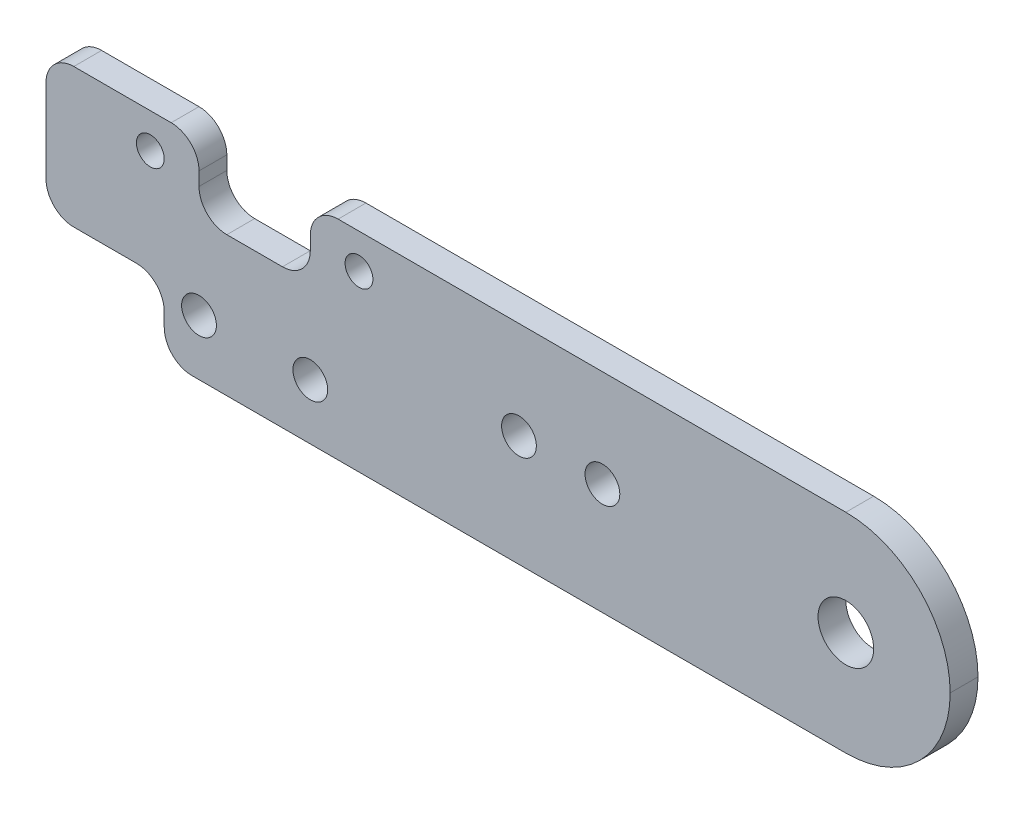
SolidWorks part; units mm, degrees
material "Thornel Mat VMA"
ref_plane "前视基准面" through (0, 0, 0) normal (0, 0, 1) x (1, 0, 0)
ref_plane "上视基准面" through (0, 0, 0) normal (0, 1, 0) x (1, 0, 0)
ref_plane "右视基准面" through (0, 0, 0) normal (1, 0, 0) x (0, 0, -1)
sketch "草图1" plane through (0, 0, 0) normal (0, 0, 1) x (1, 0, 0)
  line L1 (-32.5, -7.5) -> (32.5, -7.5)
  line L2 (-32.5, -7.5) -> (-32.5, 7.5)
  line L3 (-32.5, 7.5) -> (32.5, 7.5)
  line L4 (32.5, -7.5) -> (32.5, 7.5)
  line L5 (-32.5, -7.5) -> (32.5, 7.5) construction
  line L6 (-32.5, 7.5) -> (32.5, -7.5) construction
  point P0 (0, 0)
  dimension "D1" = 65
  dimension "D2" = 15
extrude "凸台-拉伸1" add sketch "草图1" along normal blind 2
fillet "圆角1" radius 7.5 2 edges at (32.5, 7.5, 1) (32.5, -7.5, 1)
sketch "草图2" plane through (0, 0, 2) normal (0, 0, 1) x (1, 0, 0)
  line L1 (-32.5, 7.5) -> (-32.5, -7.5) construction
  line L2 (25, 7.5) -> (-32.5, 7.5) construction
  circle A0 centre (25, 0) radius 2
  circle A1 centre (-25, 5) radius 1
  circle A2 centre (-10, 5) radius 1
  dimension "D1" = 4
  dimension "D2" = 2
  dimension "D3" = 2.5
  dimension "D4" = 7.5
  dimension "D5" = 15
extrude "切除-拉伸1" cut sketch "草图2" against normal blind 10
sketch "草图7" plane through (0, 0, 2) normal (0, 0, 1) x (1, 0, 0)
  line L0 (-32.5, 7.5) -> (-32.5, -7.5) construction
  line L1 (-32.5, -2.5) -> (-22.5, -2.5)
  line L2 (-32.5, -2.5) -> (-32.5, -7.5)
  line L3 (-32.5, -7.5) -> (-22.5, -7.5)
  line L4 (-22.5, -2.5) -> (-22.5, -7.5)
  line L5 (-32.5, -2.5) -> (-22.5, -7.5) construction
  line L6 (-32.5, -7.5) -> (-22.5, -2.5) construction
  line L7 (-32.5, -7.5) -> (25, -7.5) construction
  point P4 (-27.5, -5)
  dimension "D1" = 10
  dimension "D2" = 5
extrude "切除-拉伸5" [suppressed] cut sketch "草图7" against normal blind 10
fillet "圆角2" [suppressed] radius 2
sketch "草图4" plane through (0, 0, 0) normal (0, 0, -1) x (-1, 0, 0)
  line L0 (32.5, 7.5) -> (32.5, -7.5) construction
  line L2 (32.5, -7.5) -> (-25, -7.5) construction
  circle A0 centre (21.5, -3.5) radius 1.25
  circle A1 centre (13.5, -3.5) radius 1.25
  dimension "D1" = 11
  dimension "D2" = 4
  dimension "D3" = 8
  dimension "D4" = 2.5
extrude "切除-拉伸3" cut sketch "草图4" against normal blind 10
sketch "草图8" plane through (0, 0, 2) normal (0, 0, 1) x (1, 0, 0)
  line L0 (25, 7.5) -> (-32.5, 7.5) construction
  circle A0 centre (7.5, 0.5) radius 1.25
  circle A1 centre (1.5, 0.5) radius 1.25
  arc A2 (32.5, 0) -> (25, 7.5) centre (25, 0) ccw construction
  dimension "D1" = 6
  dimension "D2" = 2.5
  dimension "D3" = 7
  dimension "D4" = 17.5
extrude "切除-拉伸6" cut sketch "草图8" against normal blind 10
sketch "草图9" plane through (0, 0, 2) normal (0, 0, 1) x (1, 0, 0)
  line L0 (25, 7.5) -> (-32.5, 7.5) construction
  line L1 (-21.5, 7.5) -> (-13.5, 7.5)
  line L2 (-21.5, 7.5) -> (-21.5, 2.5297)
  line L3 (-21.5, 2.5297) -> (-13.5, 2.5297)
  line L4 (-13.5, 7.5) -> (-13.5, 2.5297)
  line L5 (-21.5, 7.5) -> (-13.5, 2.5297) construction
  line L6 (-21.5, 2.5297) -> (-13.5, 7.5) construction
  line L7 (-32.5, 7.5) -> (-32.5, -7.5) construction
  point P4 (-17.5, 5.0149)
  dimension "D1" = 15
  dimension "D2" = 8
extrude "切除-拉伸7" cut sketch "草图9" against normal blind 10
sketch "草图10" plane through (0, 0, 2) normal (0, 0, 1) x (1, 0, 0)
  line L1 (-32.5, -7.5) -> (-24, -7.5)
  line L2 (-32.5, -7.5) -> (-32.5, -2.5)
  line L3 (-32.5, -2.5) -> (-24, -2.5)
  line L4 (-24, -7.5) -> (-24, -2.5)
  line L5 (-32.5, -7.5) -> (-24, -2.5) construction
  line L6 (-32.5, -2.5) -> (-24, -7.5) construction
  point P4 (-28.25, -5)
  dimension "D1" = 8.5
  dimension "D2" = 5
extrude "切除-拉伸8" cut sketch "草图10" against normal blind 2
fillet "圆角3" radius 2 8 edges at (-13.5, 2.5297, 1) (-13.5, 7.5, 1) (-21.5, 7.5, 1) (-21.5, 2.5297, 1) (-32.5, 7.5, 1) (-24, -2.5, 1) (-24, -7.5, 1) (-32.5, -2.5, 1)
